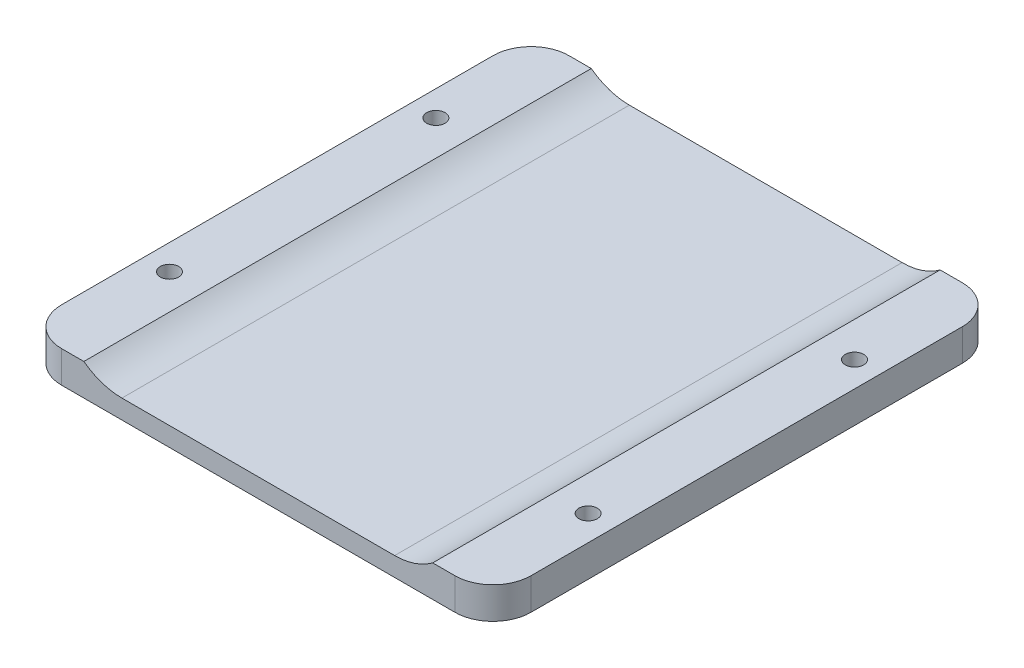
SolidWorks part; units mm, degrees
ref_plane "前视基准面" through (0, 0, 0) normal (0, 0, 1) x (1, 0, 0)
ref_plane "上视基准面" through (0, 0, 0) normal (0, 1, 0) x (1, 0, 0)
ref_plane "右视基准面" through (0, 0, 0) normal (1, 0, 0) x (0, 0, -1)
sketch "草图1" plane through (0, 0, 0) normal (0, 1, 0) x (1, 0, 0)
  line L0 (37, 0) -> (-37, 0) construction
  line L1 (-37, 40) -> (37, 40)
  line L2 (-37, 40) -> (-37, -40)
  line L3 (-37, -40) -> (37, -40)
  line L4 (37, 40) -> (37, -40)
  line L5 (-37, 40) -> (37, -40) construction
  line L6 (-37, -40) -> (37, 40) construction
  line L7 (0, 40) -> (0, -40) construction
  circle A0 centre (-33, 21) radius 1.45
  circle A1 centre (-33, -21) radius 1.45
  circle A2 centre (33, -21) radius 1.45
  circle A3 centre (33, 21) radius 1.45
  point P0 (0, 0)
  dimension "D3" = 2.9
  dimension "D1" = 74
  dimension "D2" = 80
  dimension "D4" = 33
  dimension "D5" = 21
extrude "凸台-拉伸1" add sketch "草图1" along normal blind 5
fillet "圆角1" radius 6 4 edges at (37, 2.5, -40) (-37, 2.5, -40) (-37, 2.5, 40) (37, 2.5, 40)
sketch "草图2" plane through (0, 5, 0) normal (0, 1, 0) x (1, 0, 0)
  line L0 (31, 40) -> (-31, 40) construction
  line L1 (-27.5, -40) -> (27.5, -40)
  line L2 (-27.5, -40) -> (-27.5, 40)
  line L3 (-27.5, 40) -> (27.5, 40)
  line L4 (27.5, -40) -> (27.5, 40)
  line L5 (-27.5, -40) -> (27.5, 40) construction
  line L6 (-27.5, 40) -> (27.5, -40) construction
  point P0 (0, 0)
  dimension "D1" = 55
extrude "切除-拉伸1" cut sketch "草图2" against normal blind 2
fillet "圆角2" radius 10 2 edges at (-27.5, 3, 0) (27.5, 3, 0)
